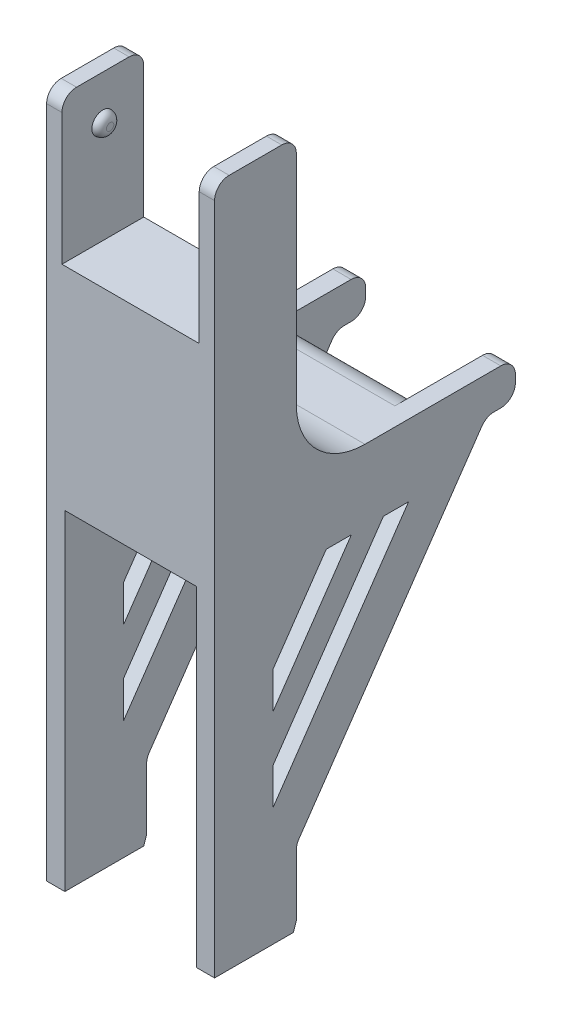
SolidWorks part; units mm, degrees
ref_plane "Front Plane" through (0, 0, 0) normal (0, 0, 1) x (1, 0, 0)
ref_plane "Top Plane" through (0, 0, 0) normal (0, 1, 0) x (1, 0, 0)
ref_plane "Right Plane" through (0, 0, 0) normal (1, 0, 0) x (0, 0, -1)
sketch "Szkic1" plane through (0, 0, 0) normal (1, 0, 0) x (0, 0, -1)
  line L2 (0, 0) -> (-10.3, 0)
  line L5 (-15, 4.7) -> (-15, 20.6)
  line L6 (-15, 20.6) -> (-20.6, 20.6)
  line L7 (-20.6, 20.6) -> (-20.6, -21.4)
  line L8 (0, 0) -> (0, -2.5)
  line L9 (0, -2.5) -> (-2, -2.5)
  line L10 (-2, -2.5) -> (-15, -21.4)
  line L11 (-15, -21.4) -> (-15, -25.9)
  line L13 (-20.6, -25.9) -> (-20.6, -21.4)
  line L17 (-20.6, -26.5) -> (-15.2, -26.5)
  line L18 (-15.2, -26.5) -> (-15, -25.9)
  line L19 (-20.6, -26.5) -> (-20.6, -25.9)
  arc A0 (-15, 4.7) -> (-10.3, 0) centre (-10.3, 4.7) ccw
  point P15 (-10.3, 4.7)
  dimension "D5" = 2.5
  dimension "D7" = 4.7
  dimension "D1" = 42
  dimension "D2" = 20.6
  dimension "D3" = 15.9
  dimension "D4" = 5.6
  dimension "D6" = 2
  dimension "D8" = 18.9
  dimension "D9" = 4.5
  dimension "D10" = 0.6
  dimension "D11" = 4.5
  dimension "D12" = 0.2
extrude "Dodanie-wyciągnięcie1" add sketch "Szkic1" along normal blind 11.5
ref_plane "Płaszczyzna dolna" through (0, 0, 20.6) normal (0, 0, 1) x (1, 0, 0)
sketch "Szkic2" plane through (0, 0, 20.6) normal (0, 0, 1) x (1, 0, 0)
  line L0 (5.75, 20.6) -> (5.75, -25.9) construction
  line L1 (11.5, 20.6) -> (0, 20.6) construction
  line L4 (10.45, 10.6) -> (1.05, 10.6)
  line L5 (10.45, 10.6) -> (10.45, 20.6)
  line L6 (10.45, 20.6) -> (1.05, 20.6)
  line L7 (1.05, 10.6) -> (1.05, 20.6)
  line L8 (10.45, 10.6) -> (1.05, 20.6) construction
  line L9 (10.45, 20.6) -> (1.05, 10.6) construction
  line L10 (10.25, -3.9) -> (1.25, -3.9)
  line L11 (10.25, -3.9) -> (10.25, -28.2703)
  line L12 (10.25, -28.2703) -> (1.25, -28.2703)
  line L13 (1.25, -3.9) -> (1.25, -28.2703)
  line L14 (10.25, -3.9) -> (1.25, -28.2703) construction
  line L15 (10.25, -28.2703) -> (1.25, -3.9) construction
  point P6 (5.75, 15.6)
  point P11 (5.75, -14.9)
  dimension "D1" = 9.4
  dimension "D2" = 10
  dimension "D3" = 9
  dimension "D4" = 11
extrude "Wytnij-wyciągnięcie1" cut sketch "Szkic2" against normal through all
ref_plane "Płaszczyzna boczna" through (11.5, 0, 0) normal (1, 0, 0) x (0, 0, -1)
sketch "Szkic3" plane through (11.5, 0, 0) normal (1, 0, 0) x (0, 0, -1)
  line L0 (-16.6, -12.7056) -> (-16.6, -10.1985)
  line L1 (-16.6, -10.1985) -> (-12.9555, -4.9)
  line L2 (-12.9555, -4.9) -> (-11.2311, -4.9)
  line L3 (-11.2311, -4.9) -> (-16.6, -12.7056)
  line L4 (-16.6, -15.8972) -> (-16.6, -18.4043)
  line L5 (-16.6, -18.4043) -> (-7.3113, -4.9)
  line L6 (-7.3113, -4.9) -> (-9.0358, -4.9)
  line L7 (-9.0358, -4.9) -> (-16.6, -15.8972)
  line L8 (-15, -21.4) -> (-2, -2.5) construction
  line L10 (-20.6, 6.325) -> (-20.6, -6.325) construction
  dimension "D1" = 4
  dimension "D2" = 21
extrude "Wytnij-wyciągnięcie2" cut sketch "Szkic3" against normal through all both and the other way through all
ref_plane "Płaszczyzna3" through (0, 0, 0) normal (0, 1, 0) x (1, 0, 0)
sketch "Szkic4" plane through (0, 0, 0) normal (0, 1, 0) x (1, 0, 0)
  line L0 (5.75, -5) -> (5.75, 0) construction
  line L2 (11.5, 0) -> (0, 0) construction
  line L4 (1.25, -5) -> (10.25, -5)
  line L5 (1.25, -5) -> (1.25, 0)
  line L6 (1.25, 0) -> (10.25, 0)
  line L7 (10.25, -5) -> (10.25, 0)
  line L8 (1.25, -5) -> (10.25, 0) construction
  line L9 (1.25, 0) -> (10.25, -5) construction
  point P6 (5.75, -2.5)
  dimension "D1" = 9
  dimension "D2" = 5
extrude "Wytnij-wyciągnięcie3" cut sketch "Szkic4" against normal blind 10
fillet "Zaokrąglenie1" radius 2 2 edges at (5.75, -3.9, 5) (5.75, 0, 5)
fillet "Zaokrąglenie2" radius 1 12 edges at (0.625, 0, 0) (0.625, -2.5, 0) (10.875, -2.5, 0) (10.875, 0, 0) (10.975, 20.6, 20.6) (10.975, 20.6, 15) (0.525, 20.6, 20.6) (0.525, 20.6, 15) (0.625, -2.5, 2) (10.875, -2.5, 2) (0.625, -21.4, 15) (10.875, -21.4, 15)
ref_plane "Płaszczyzna4" through (10.45, 0, 0) normal (-1, 0, 0) x (0, 0, 1)
sketch "Szkic5" plane through (10.45, 0, 0) normal (-1, 0, 0) x (0, 0, 1)
  line L3 (17.8, 20.6) -> (17.8, 10.6) construction
  line L4 (16, 20.6) -> (19.6, 20.6) construction
  line L5 (15, 10.6) -> (20.6, 10.6) construction
  circle A0 centre (17.8, 17.6) radius 0.75
  dimension "D1" = 1.5
  dimension "D2" = 3
extrude "Dodanie-wyciągnięcie2" add sketch "Szkic5" along normal blind 0.5
fillet "Zaokrąglenie3" radius 0.5 1 edges at (9.95, 16.85, 17.8)
ref_plane "Płaszczyzna5" through (5.75, 0, 0) normal (1, 0, 0) x (0, 0, -1)
mirror "Lustro2" about plane through (5.75, 0, 0) normal (1, 0, 0) of bodies 113 115
